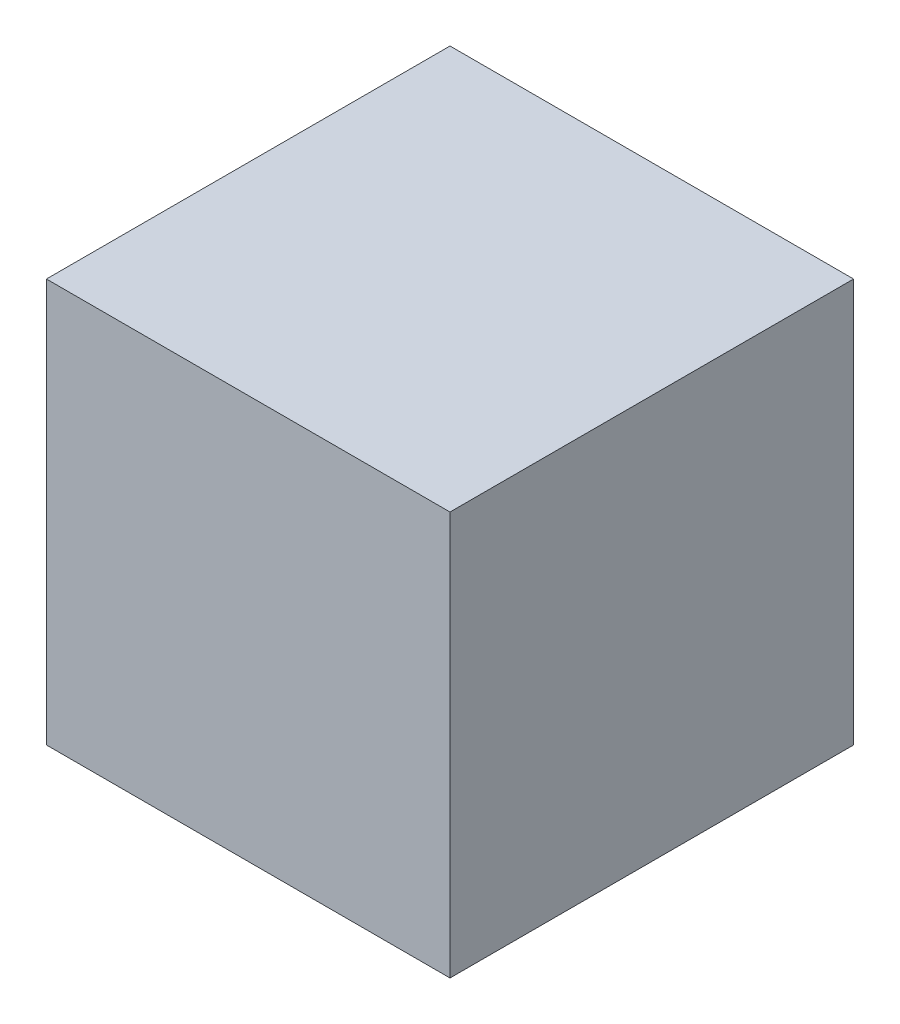
SolidWorks part; units mm, degrees
ref_plane "Plan de face" through (0, 0, 0) normal (0, 0, 1) x (1, 0, 0)
ref_plane "Plan de dessus" through (0, 0, 0) normal (0, 1, 0) x (1, 0, 0)
ref_plane "Plan de droite" through (0, 0, 0) normal (1, 0, 0) x (0, 0, -1)
sketch "Esquisse1" plane through (0, 0, 0) normal (0, 0, 1) x (1, 0, 0)
  line L1 (-100, 100) -> (100, 100)
  line L2 (-100, 100) -> (-100, -100)
  line L3 (-100, -100) -> (100, -100)
  line L4 (100, 100) -> (100, -100)
  point P4 (0, 100)
  point P6 (-100, 0)
  dimension "D1" = 200
  dimension "D2" = 200
extrude "Boss.-Extru.1" add sketch "Esquisse1" along normal blind 100 and the other way blind 100
scale "Echelle1" scale about centroid uniform scaling yes scale factor 0.001
